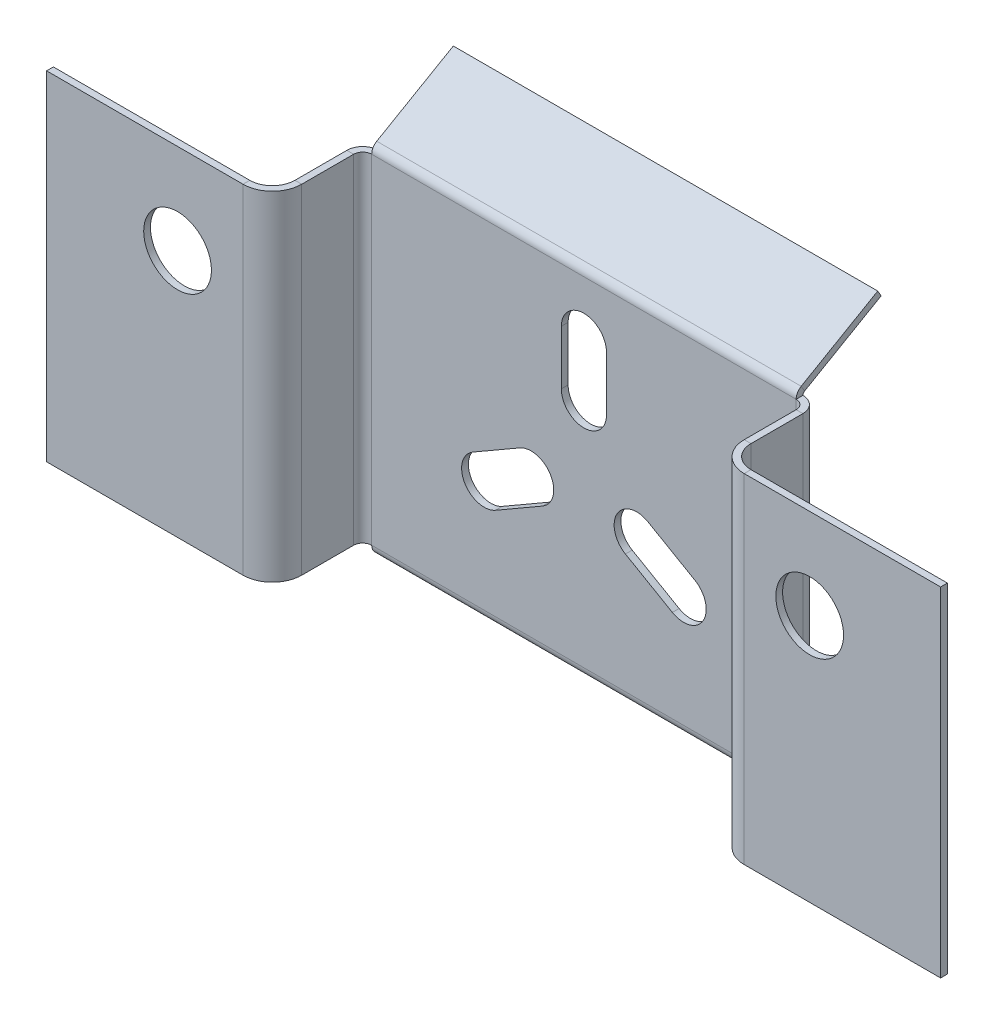
SolidWorks part; units mm, degrees
note: The reader was unsure of these and kept them because the rebuilt part matched: flange length of "Edge-Flange1", "Edge-Flange2", "Edge-Flange3", "Edge-Flange4", "Edge-Flange5", "Edge-Flange6".
ref_plane "Front Plane" through (0, 0, 0) normal (0, 0, 1) x (1, 0, 0)
ref_plane "Top Plane" through (0, 0, 0) normal (0, 1, 0) x (1, 0, 0)
ref_plane "Right Plane" through (0, 0, 0) normal (1, 0, 0) x (0, 0, -1)
sketch "Sketch1" plane through (0, 0, 0) normal (0, 0, 1) x (1, 0, 0)
  line L0 (0, 25.5) -> (0, 13.5) construction
  line L1 (-47, 37.5) -> (47, 37.5)
  line L2 (-47, 37.5) -> (-47, -37.5)
  line L3 (-47, -37.5) -> (47, -37.5)
  line L4 (47, 37.5) -> (47, -37.5)
  line L5 (-47, 37.5) -> (47, -37.5) construction
  line L6 (-47, -37.5) -> (47, 37.5) construction
  line L7 (5, 25.5) -> (5, 13.5)
  line L8 (-5, 25.5) -> (-5, 13.5)
  line L9 (22.0836, -12.75) -> (11.6913, -6.75) construction
  line L10 (19.5836, -17.0801) -> (9.1913, -11.0801)
  line L11 (24.5836, -8.4199) -> (14.1913, -2.4199)
  line L12 (-22.0836, -12.75) -> (-11.6913, -6.75) construction
  line L13 (-24.5836, -8.4199) -> (-14.1913, -2.4199)
  line L14 (-19.5836, -17.0801) -> (-9.1913, -11.0801)
  arc A0 (5, 25.5) -> (-5, 25.5) centre (0, 25.5) ccw
  arc A1 (-5, 13.5) -> (5, 13.5) centre (0, 13.5) ccw
  arc A2 (19.5836, -17.0801) -> (24.5836, -8.4199) centre (22.0836, -12.75) ccw
  arc A3 (14.1913, -2.4199) -> (9.1913, -11.0801) centre (11.6913, -6.75) ccw
  arc A4 (-24.5836, -8.4199) -> (-19.5836, -17.0801) centre (-22.0836, -12.75) ccw
  arc A5 (-9.1913, -11.0801) -> (-14.1913, -2.4199) centre (-11.6913, -6.75) ccw
  point P0 (0, 0)
  point P8 (0, 19.5)
  point P18 (16.8875, -9.75)
  point P25 (-16.8875, -9.75)
  point P30 (0, 0)
  dimension "D4" = 5
  dimension "D1" = 75
  dimension "D2" = 94
  dimension "D3" = 12
  dimension "D5" = 13.5
  dimension "D6" = 3
base flange "Base-Flange1" sketch "Sketch1" thickness 1.5 reverse thickness direction no parameters "D1"=0.7366
edge flange "Edge-Flange1" sketch "Sketch8" flange angle 90 flange length 20 flange position bend outside bend radius 2 thickness 1.5 relief rectangular parameters "D6"=10
sketch "Sketch8" plane through (47, 0, 0) normal (1, 0, 0) x (0, 1, 0)
  line L0 (-37.5, 0) -> (37.5, 0) construction
  line L1 (-37.5, 0) -> (37.5, 0)
  line L2 (-37.5, 0) -> (-37.5, 18.5)
  line L3 (-37.5, 18.5) -> (37.5, 18.5)
  line L4 (37.5, 18.5) -> (37.5, 0)
bend "EdgeBend1" bend radius 2 bend angle 90 parameters "D5"=1
edge flange "Edge-Flange2" sketch "Sketch11" flange angle 90 flange length 50 flange position material outside bend radius 5 thickness 1.5 relief rectangular parameters "D6"=10
sketch "Sketch11" plane through (50.5, 0, 18.5) normal (0, 0, 1) x (0, -1, 0)
  line L0 (-37.5, 0) -> (37.5, 0) construction
  line L1 (-37.5, 0) -> (37.5, 0)
  line L2 (-37.5, 0) -> (-37.5, 48.5)
  line L3 (-37.5, 48.5) -> (37.5, 48.5)
  line L4 (37.5, 48.5) -> (37.5, 0)
bend "EdgeBend2" bend radius 5 bend angle 90 parameters "D5"=2
edge flange "Edge-Flange3" sketch "Sketch14" flange angle 90 flange length 20 flange position bend outside bend radius 2 thickness 1.5 relief rectangular parameters "D6"=10
sketch "Sketch14" plane through (-47, 0, 0) normal (-1, 0, 0) x (0, -1, 0)
  line L0 (-37.5, 0) -> (37.5, 0) construction
  line L1 (-37.5, 0) -> (37.5, 0)
  line L2 (-37.5, 0) -> (-37.5, 18.5)
  line L3 (-37.5, 18.5) -> (37.5, 18.5)
  line L4 (37.5, 18.5) -> (37.5, 0)
bend "EdgeBend3" bend radius 2 bend angle 90 parameters "D5"=3
edge flange "Edge-Flange4" sketch "Sketch17" flange angle 90 flange length 50 flange position material outside bend radius 5 thickness 1.5 relief rectangular parameters "D6"=10
sketch "Sketch17" plane through (-50.5, 0, 18.5) normal (0, 0, 1) x (0, 1, 0)
  line L0 (-37.5, 0) -> (37.5, 0) construction
  line L1 (-37.5, 0) -> (37.5, 0)
  line L2 (-37.5, 0) -> (-37.5, 48.5)
  line L3 (-37.5, 48.5) -> (37.5, 48.5)
  line L4 (37.5, 48.5) -> (37.5, 0)
bend "EdgeBend4" bend radius 5 bend angle 90 parameters "D5"=4
sketch "Sketch18" plane through (0, 0, 20) normal (0, 0, 1) x (1, 0, 0)
  line L0 (99, 37.5) -> (55.5, 37.5) construction
  line L1 (99, -37.5) -> (99, 37.5) construction
  line L2 (0, 47.6258) -> (0, -52.6891) construction
  circle A0 centre (70, 17.5) radius 7.5
  circle A1 centre (-70, 17.5) radius 7.5
  dimension "D1" = 15
  dimension "D2" = 20
  dimension "D3" = 29
extrude "Cut-Extrude1" cut sketch "Sketch18" against normal blind 10
edge flange "Edge-Flange5" sketch "Sketch21" flange angle 120 flange length 20 flange position bend outside bend radius 0.7366 thickness 1.5 relief rectangular parameters "D6"=10
sketch "Sketch21" plane through (0, 37.5, -1.5) normal (0, 0.866, 0.5) x (1, 0, 0)
  line L0 (47, 0) -> (-47, 0) construction
  line L1 (47, 0) -> (-47, 0)
  line L2 (-47, 0) -> (-47, 20)
  line L3 (-47, 20) -> (47, 20)
  line L4 (47, 20) -> (47, 0)
bend "EdgeBend5" bend radius 0.7366 bend angle 60 parameters "D5"=5
edge flange "Edge-Flange6" sketch "Sketch24" flange angle 120 flange length 20 flange position bend outside bend radius 0.7366 thickness 1.5 relief rectangular parameters "D6"=10
sketch "Sketch24" plane through (0, -37.5, -1.5) normal (0, -0.866, 0.5) x (-1, 0, 0)
  line L0 (47, 0) -> (-47, 0) construction
  line L1 (47, 0) -> (-47, 0)
  line L2 (-47, 0) -> (-47, 20)
  line L3 (-47, 20) -> (47, 20)
  line L4 (47, 20) -> (47, 0)
bend "EdgeBend6" bend radius 0.7366 bend angle 60 parameters "D5"=6
sketch "Bend-Lines1" [suppressed] plane through (0, 0, 0) normal (0, 1, 0) x (1, 0, 0)
sketch "Bounding-Box1" [suppressed] plane through (0, 0, 0) normal (0, 1, 0) x (1, 0, 0)
sheet metal parameters "Sheet-Metal1" thickness 1.5 parameters "D1"=0.7366
flat pattern "Flat-Pattern1" [suppressed]
sketch "Bend-Lines2" plane through (0, 0, 0) normal (0, 1, 0) x (1, 0, 0)
sketch3d "Bounding-Box2" [suppressed]
  line L0 (47, -37.5, 0) -> (-47, -37.5, 0) construction
  line L1 (47, 37.5, 0) -> (-47, 37.5, 0) construction
  line L2 (47, -37.5, 0) -> (47, 37.5, 0) construction
  line L3 (-47, -37.5, 0) -> (-47, 37.5, 0) construction
sheet metal parameters "Sheet-Metal2" thickness 1.5 parameters "D1"=0.7366
flat pattern "Flat-Pattern1"
sketch "Bend-Lines2" plane through (0, 0, 0) normal (0, 0, 1) x (1, 0, 0)
  line L0 (47.1598, -37.5) -> (47.1598, 37.5) construction
  line L1 (47.1598, -37.5) -> (47.1598, 37.5) construction
sketch3d "Bounding-Box2" [suppressed]
  line L0 (-47, -37.5, 0) -> (65.8197, -37.5, 0) construction
  line L1 (-47, 37.5, 0) -> (65.8197, 37.5, 0) construction
  line L2 (-47, -37.5, 0) -> (-47, 37.5, 0) construction
  line L3 (65.8197, -37.5, 0) -> (65.8197, 37.5, 0) construction
bend of the flat pattern "Flatten-<EdgeBend1>1"
sheet metal parameters "Sheet-Metal3" thickness 1.5 parameters "D1"=0.7366
flat pattern "Flat-Pattern1"
sketch "Bend-Lines2" plane through (0, 0, 0) normal (0, 0, 1) x (1, 0, 0)
  line L0 (47.1598, -37.5) -> (47.1598, 37.5) construction
  line L1 (47.1598, -37.5) -> (47.1598, 37.5) construction
  line L2 (65.3357, -37.5) -> (65.3357, 37.5) construction
  line L3 (65.3357, -37.5) -> (65.3357, 37.5) construction
sketch3d "Bounding-Box2" [suppressed]
  line L0 (-47, -37.5, 0) -> (113.3518, -37.5, 0) construction
  line L1 (-47, 37.5, 0) -> (113.3518, 37.5, 0) construction
  line L2 (-47, -37.5, 0) -> (-47, 37.5, 0) construction
  line L3 (113.3518, -37.5, 0) -> (113.3518, 37.5, 0) construction
bend of the flat pattern "Flatten-<EdgeBend1>1"
bend of the flat pattern "Flatten-<EdgeBend2>1"
sheet metal parameters "Sheet-Metal4" thickness 1.5 parameters "D1"=0.7366
flat pattern "Flat-Pattern1"
sketch "Bend-Lines2" plane through (0, 0, 0) normal (0, 0, 1) x (1, 0, 0)
  line L0 (47.1598, -37.5) -> (47.1598, 37.5) construction
  line L1 (47.1598, -37.5) -> (47.1598, 37.5) construction
  line L2 (65.3357, -37.5) -> (65.3357, 37.5) construction
  line L3 (65.3357, -37.5) -> (65.3357, 37.5) construction
  line L4 (-47.1598, 37.5) -> (-47.1598, -37.5) construction
  line L5 (-47.1598, 37.5) -> (-47.1598, -37.5) construction
sketch3d "Bounding-Box2" [suppressed]
  line L0 (-65.8197, -37.5, 0) -> (113.3518, -37.5, 0) construction
  line L1 (-65.8197, 37.5, 0) -> (113.3518, 37.5, 0) construction
  line L2 (-65.8197, -37.5, 0) -> (-65.8197, 37.5, 0) construction
  line L3 (113.3518, -37.5, 0) -> (113.3518, 37.5, 0) construction
bend of the flat pattern "Flatten-<EdgeBend1>1"
bend of the flat pattern "Flatten-<EdgeBend2>1"
bend of the flat pattern "Flatten-<EdgeBend3>1"
sheet metal parameters "Sheet-Metal5" thickness 1.5 parameters "D1"=0.7366
flat pattern "Flat-Pattern1"
sketch "Bend-Lines2" plane through (0, 0, 0) normal (0, 0, 1) x (1, 0, 0)
  line L0 (47.1598, -37.5) -> (47.1598, 37.5) construction
  line L1 (47.1598, -37.5) -> (47.1598, 37.5) construction
  line L2 (65.3357, -37.5) -> (65.3357, 37.5) construction
  line L3 (65.3357, -37.5) -> (65.3357, 37.5) construction
  line L4 (-47.1598, 37.5) -> (-47.1598, -37.5) construction
  line L5 (-47.1598, 37.5) -> (-47.1598, -37.5) construction
  line L6 (-65.3357, 37.5) -> (-65.3357, -37.5) construction
  line L7 (-65.3357, 37.5) -> (-65.3357, -37.5) construction
sketch3d "Bounding-Box2" [suppressed]
  line L0 (-113.3518, -37.5, 0) -> (113.3518, -37.5, 0) construction
  line L1 (-113.3518, 37.5, 0) -> (113.3518, 37.5, 0) construction
  line L2 (-113.3518, -37.5, 0) -> (-113.3518, 37.5, 0) construction
  line L3 (113.3518, -37.5, 0) -> (113.3518, 37.5, 0) construction
bend of the flat pattern "Flatten-<EdgeBend1>1"
bend of the flat pattern "Flatten-<EdgeBend2>1"
bend of the flat pattern "Flatten-<EdgeBend3>1"
bend of the flat pattern "Flatten-<EdgeBend4>1"
sheet metal parameters "Sheet-Metal6" thickness 1.5 parameters "D1"=0.7366
flat pattern "Flat-Pattern1"
sketch "Bend-Lines2" plane through (0, 0, 0) normal (0, 0, 1) x (1, 0, 0)
  line L0 (47.1598, -37.5) -> (47.1598, 37.5) construction
  line L1 (47.1598, -37.5) -> (47.1598, 37.5) construction
  line L2 (65.3357, -37.5) -> (65.3357, 37.5) construction
  line L3 (65.3357, -37.5) -> (65.3357, 37.5) construction
  line L4 (-47.1598, 37.5) -> (-47.1598, -37.5) construction
  line L5 (-47.1598, 37.5) -> (-47.1598, -37.5) construction
  line L6 (-65.3357, 37.5) -> (-65.3357, -37.5) construction
  line L7 (-65.3357, 37.5) -> (-65.3357, -37.5) construction
sketch3d "Bounding-Box2" [suppressed]
  line L0 (-113.3518, -37.5, 0) -> (113.3518, -37.5, 0) construction
  line L1 (-113.3518, 37.5, 0) -> (113.3518, 37.5, 0) construction
  line L2 (-113.3518, -37.5, 0) -> (-113.3518, 37.5, 0) construction
  line L3 (113.3518, -37.5, 0) -> (113.3518, 37.5, 0) construction
bend of the flat pattern "Flatten-<EdgeBend1>1"
bend of the flat pattern "Flatten-<EdgeBend2>1"
bend of the flat pattern "Flatten-<EdgeBend3>1"
bend of the flat pattern "Flatten-<EdgeBend4>1"
sheet metal parameters "Sheet-Metal7" thickness 1.5 parameters "D1"=0.7366
flat pattern "Flat-Pattern1"
sketch "Bend-Lines2" plane through (0, 0, 0) normal (0, 0, 1) x (1, 0, 0)
  line L0 (47.1598, -37.5) -> (47.1598, 37.5) construction
  line L1 (47.1598, -37.5) -> (47.1598, 37.5) construction
  line L2 (65.3357, -37.5) -> (65.3357, 37.5) construction
  line L3 (65.3357, -37.5) -> (65.3357, 37.5) construction
  line L4 (-47.1598, 37.5) -> (-47.1598, -37.5) construction
  line L5 (-47.1598, 37.5) -> (-47.1598, -37.5) construction
  line L6 (-65.3357, 37.5) -> (-65.3357, -37.5) construction
  line L7 (-65.3357, 37.5) -> (-65.3357, -37.5) construction
  line L8 (45, 37.8531) -> (-45, 37.8531) construction
  line L9 (45, 37.8531) -> (-45, 37.8531) construction
sketch3d "Bounding-Box2" [suppressed]
  line L0 (-113.3518, -37.5, 0) -> (113.3518, -37.5, 0) construction
  line L1 (-113.3518, 58.2062, 0) -> (113.3518, 58.2062, 0) construction
  line L2 (-113.3518, -37.5, 0) -> (-113.3518, 58.2062, 0) construction
  line L3 (113.3518, -37.5, 0) -> (113.3518, 58.2062, 0) construction
bend of the flat pattern "Flatten-<EdgeBend1>1"
bend of the flat pattern "Flatten-<EdgeBend2>1"
bend of the flat pattern "Flatten-<EdgeBend3>1"
bend of the flat pattern "Flatten-<EdgeBend4>1"
bend of the flat pattern "Flatten-<EdgeBend5>1"
sheet metal parameters "Sheet-Metal8" thickness 1.5 parameters "D1"=0.7366
flat pattern "Flat-Pattern1"
sketch "Bend-Lines2" plane through (0, 0, 0) normal (0, 0, 1) x (1, 0, 0)
  line L0 (49.1598, -37.5) -> (49.1598, 37.5) construction
  line L1 (49.1598, -37.5) -> (49.1598, 37.5) construction
  line L2 (67.3357, -37.5) -> (67.3357, 37.5) construction
  line L3 (67.3357, -37.5) -> (67.3357, 37.5) construction
  line L4 (-49.1598, 37.5) -> (-49.1598, -37.5) construction
  line L5 (-49.1598, 37.5) -> (-49.1598, -37.5) construction
  line L6 (-67.3357, 37.5) -> (-67.3357, -37.5) construction
  line L7 (-67.3357, 37.5) -> (-67.3357, -37.5) construction
  line L8 (47, 38.2784) -> (-47, 38.2784) construction
  line L9 (47, 38.2784) -> (-47, 38.2784) construction
  line L10 (-47, -38.2784) -> (47, -38.2784) construction
  line L11 (-47, -38.2784) -> (47, -38.2784) construction
sketch3d "Bounding-Box2" [suppressed]
  line L0 (-115.3518, -58.6315, 0) -> (115.3518, -58.6315, 0) construction
  line L1 (-115.3518, 58.6315, 0) -> (115.3518, 58.6315, 0) construction
  line L2 (-115.3518, -58.6315, 0) -> (-115.3518, 58.6315, 0) construction
  line L3 (115.3518, -58.6315, 0) -> (115.3518, 58.6315, 0) construction
bend of the flat pattern "Flatten-<EdgeBend1>1"
bend of the flat pattern "Flatten-<EdgeBend2>1"
bend of the flat pattern "Flatten-<EdgeBend3>1"
bend of the flat pattern "Flatten-<EdgeBend4>1"
bend of the flat pattern "Flatten-<EdgeBend5>1"
bend of the flat pattern "Flatten-<EdgeBend6>1"
